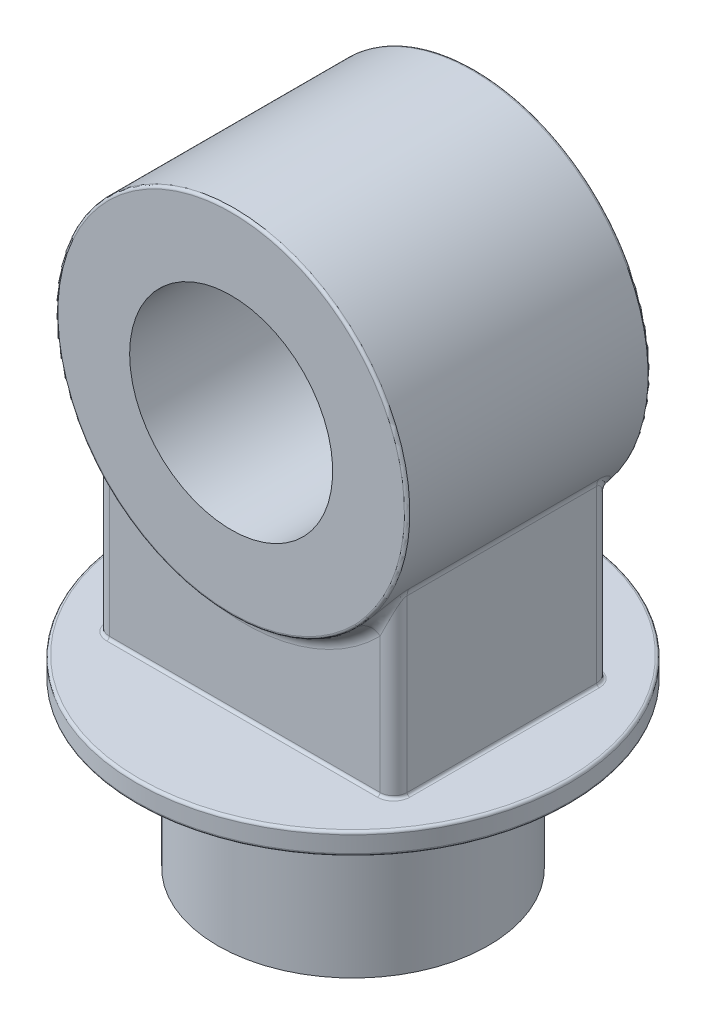
SolidWorks part; units mm, degrees
ref_plane "Front Plane" through (0, 0, 0) normal (0, 0, 1) x (1, 0, 0)
ref_plane "Top Plane" through (0, 0, 0) normal (0, 1, 0) x (1, 0, 0)
ref_plane "Right Plane" through (0, 0, 0) normal (1, 0, 0) x (0, 0, -1)
sketch "Sketch1" plane through (0, 0, 0) normal (0, 1, 0) x (1, 0, 0)
  circle A0 centre (0, 0) radius 100
  dimension "D1" = 200
extrude "Boss-Extrude1" add sketch "Sketch1" along normal blind 120
sketch "Sketch2" plane through (0, 120, 0) normal (0, 1, 0) x (1, 0, 0)
  circle A0 centre (0, 0) radius 160
  dimension "D1" = 320
extrude "Boss-Extrude2" add sketch "Sketch2" along normal blind 16
sketch "Sketch3" plane through (0, 0, 0) normal (0, 0, 1) x (1, 0, 0)
  line L0 (0, 136) -> (0, 336) construction
  line L1 (160, 136) -> (-160, 136) construction
  line L2 (0, 136) -> (0, 120) construction
  circle A0 centre (0, 336) radius 75
  circle A1 centre (0, 336) radius 130
  dimension "D1" = 260
  dimension "D2" = 150
  dimension "D3" = 200
extrude "Boss-Extrude3" add sketch "Sketch3" along normal mid plane 180 separate body
sketch "Sketch4" plane through (0, 136, 0) normal (0, 1, 0) x (1, 0, 0)
  line L1 (-110, -80) -> (110, -80)
  line L2 (-110, -80) -> (-110, 80)
  line L3 (-110, 80) -> (110, 80)
  line L4 (110, -80) -> (110, 80)
  line L5 (-110, -80) -> (110, 80) construction
  line L6 (-110, 80) -> (110, -80) construction
  point P0 (0, 0)
  dimension "D1" = 160
  dimension "D2" = 220
extrude "Boss-Extrude4" add sketch "Sketch4" along normal up to next
fillet "Fillet1" radius 10 8 edges at (-110, 266.718, 0) (0, 206, -80) (0, 206, 80) (-110, 201.359, -80) (-110, 201.359, 80) (110, 201.359, -80) (110, 266.718, 0) (110, 201.359, 80)
fillet "Fillet2" radius 2 14 edges at (-107.0711, 136, 77.0711) (-110, 136, 0) (-107.0711, 136, -77.0711) (0, 136, -80) (107.0711, 136, -77.0711) (110, 136, 0) (107.0711, 136, 77.0711) (0, 206, -90) (0, 206, 90) (0, 120, 160) (0, 136, 160) (0, 136, 80) (0, 466, -90) (0, 466, 90)
